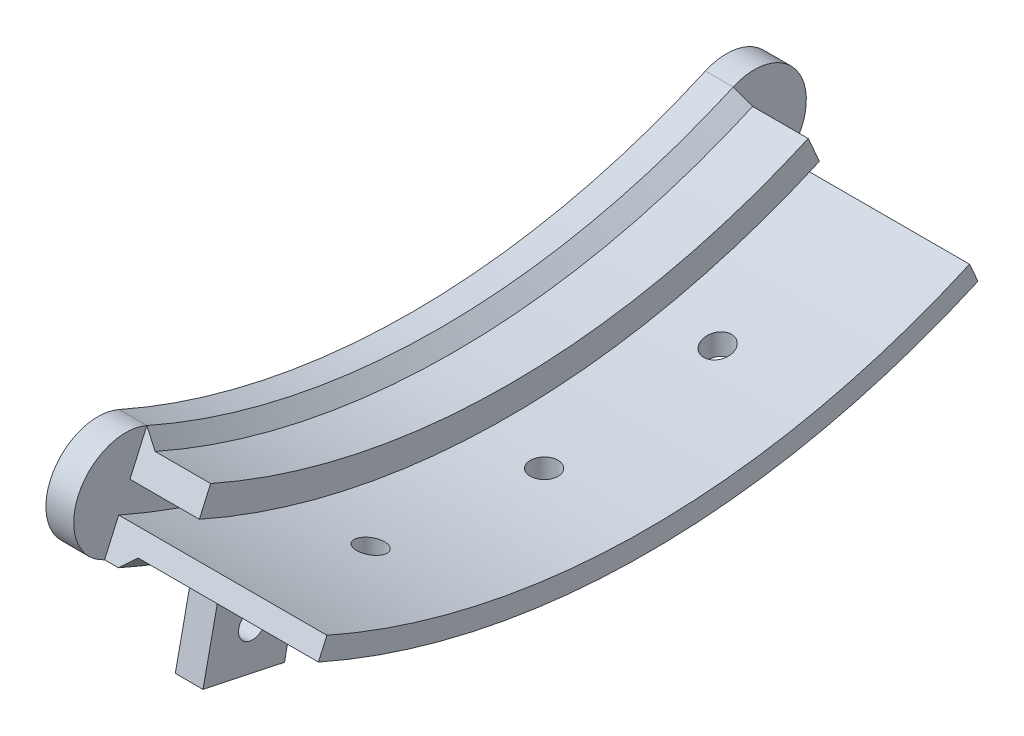
SolidWorks part; units mm, degrees
ref_plane "Front Plane" through (0, 0, 0) normal (0, 0, 1) x (1, 0, 0)
ref_plane "Top Plane" through (0, 0, 0) normal (0, 1, 0) x (1, 0, 0)
ref_plane "Right Plane" through (0, 0, 0) normal (1, 0, 0) x (0, 0, -1)
sketch "Sketch1" plane through (0, 0, 0) normal (1, 0, 0) x (0, 0, -1)
  line L0 (0, 0) -> (0, -110) construction
  line L1 (0, -110) -> (81.9959, -110) construction
  line L2 (-40, -90) -> (40, -90) construction
  line L3 (0, 0) -> (-44.6752, -100.5193) construction
  line L4 (0, 0) -> (44.6752, -100.5193) construction
  line L5 (-44.6752, -100.5193) -> (-43.0507, -96.864)
  line L6 (44.6752, -100.5193) -> (43.0507, -96.864)
  arc A0 (-44.6752, -100.5193) -> (44.6752, -100.5193) centre (0, 0) ccw
  arc A1 (-43.0507, -96.864) -> (43.0507, -96.864) centre (0, 0) ccw
  point P7 (0, -90)
  dimension "D1" = 110
  dimension "D2" = 80
  dimension "D3" = 20
  dimension "D4" = 110
  dimension "D5" = 4
extrude "Boss-Extrude1" add sketch "Sketch1" along normal blind 10
sketch "Sketch2" plane through (0, 0, 0) normal (1, 0, 0) x (0, 0, -1)
  line L0 (0, -106) -> (0, -140.9487) construction
  line L1 (0, -90) -> (0, -76.6101) construction
  line L2 (-40, -90) -> (40, -90) construction
  line L3 (0, 0) -> (0, -110) construction
  line L4 (0, -90) -> (-40, -90) construction
  line L5 (0, -90) -> (40, -90) construction
  line L6 (0, 0) -> (-20, -90) construction
  line L11 (0, -119) -> (48.3305, -108.7436) construction
  line L12 (24.1652, -113.8718) -> (28.2786, -133.255) construction
  line L13 (0, -57.7628) -> (0, -68.1897) construction
  line L14 (18.8027, -117.5051) -> (22.4093, -134.5005)
  line L15 (30.5413, -115.014) -> (34.1479, -132.0094)
  line L16 (22.4093, -134.5005) -> (34.1479, -132.0094)
  line L17 (18.2959, -115.1173) -> (22.4093, -134.5005) construction
  line L18 (30.0345, -112.6262) -> (34.1479, -132.0094) construction
  line L19 (-22.4093, -134.5005) -> (-34.1479, -132.0094)
  line L20 (-30.5413, -115.014) -> (-34.1479, -132.0094)
  line L21 (-18.8027, -117.5051) -> (-22.4093, -134.5005)
  arc A0 (-48.3305, -108.7436) -> (-42.2384, -95.0364) centre (-45.2844, -101.89) cw
  arc A1 (42.2384, -95.0364) -> (48.3305, -108.7436) centre (45.2844, -101.89) cw
  arc A2 (-42.2384, -95.0364) -> (42.2384, -95.0364) centre (0, 0) ccw
  arc A3 (-42.2384, -95.0364) -> (42.2384, -95.0364) centre (0, 0) ccw
  arc A5 (-48.3305, -108.7436) -> (48.3305, -108.7436) centre (0, 0) ccw
  arc A6 (-48.3305, -108.7436) -> (-30.5413, -115.014) centre (0, 0) ccw
  arc A8 (-43.0507, -96.864) -> (43.0507, -96.864) centre (0, 0) ccw construction
  circle A9 centre (27.0331, -127.3857) radius 2
  arc A10 (30.5413, -115.014) -> (48.3305, -108.7436) centre (0, 0) ccw
  circle A11 centre (-27.0331, -127.3857) radius 2
  arc A12 (-18.8027, -117.5051) -> (18.8027, -117.5051) centre (0, 0) ccw
  dimension "D5" = 4
  dimension "D3" = 6
  dimension "D4" = 6
  dimension "D6" = 6
  dimension "D1" = 2
  dimension "D2" = 13
extrude "Boss-Extrude3" add sketch "Sketch2" against normal blind 4
sketch "Sketch3" plane through (0, 0, 0) normal (1, 0, 0) x (0, 0, -1)
  line L0 (0, 0) -> (-76.9177, -173.0648) construction
  line L2 (0, 0) -> (0, -66.4356) construction
  line L3 (0, 0) -> (0, -110) construction
  line L4 (0, 0) -> (76.9177, -173.0648) construction
  line L5 (44.6752, -100.5193) -> (43.0507, -96.864) construction
  line L6 (-47.5182, -106.916) -> (-46.2998, -104.1745)
  line L7 (47.5182, -106.916) -> (46.2998, -104.1745)
  arc A0 (-44.6752, -100.5193) -> (44.6752, -100.5193) centre (0, 0) ccw construction
  arc A1 (-46.2998, -104.1745) -> (46.2998, -104.1745) centre (0, 0) ccw
  arc A2 (-47.5182, -106.916) -> (47.5182, -106.916) centre (0, 0) ccw
  dimension "D1" = 4
  dimension "D2" = 3
extrude "Boss-Extrude4" add sketch "Sketch3" along normal blind 30
sketch "Sketch4" plane through (0, 0, 0) normal (0, 1, 0) x (1, 0, 0)
  line L0 (15, 47.5182) -> (15, -47.5182) construction
  line L1 (0, 47.5182) -> (30, 47.5182) construction
  line L2 (0, 47.5182) -> (0, -47.5182) construction
  line L3 (0, -47.5182) -> (30, -47.5182) construction
  line L4 (30, 47.5182) -> (30, -47.5182) construction
  line L5 (15, 0) -> (86.7317, 0) construction
  circle A0 centre (15, 25) radius 2
  circle A1 centre (15, -25) radius 2
  circle A2 centre (15, 0) radius 2
  dimension "D1" = 4
  dimension "D3" = 4
  dimension "D2" = 25
extrude "Cut-Extrude1" cut sketch "Sketch4" against normal through all both and the other way through all
chamfer "Chamfer1" distance 4 angle 45 1 edges at (0, -117, 0)
chamfer "Chamfer2" distance 4 angle 45 4 edges at (-1, -115.014, -30.5413) (-1, -117.5051, -18.8027) (-1, -117.5051, 18.8027) (-1, -115.014, 30.5413) first distance on face at (-0.8, -111.393, -41.2646) first distance on face at (-1.4, -124.891, -20.37) first distance on face at (-1, -118.2526, 0) first distance on face at (-1.4, -122.3999, 32.1086)
chamfer "Chamfer5" distance 2 angle 45 1 edges at (0, -106, 0)
